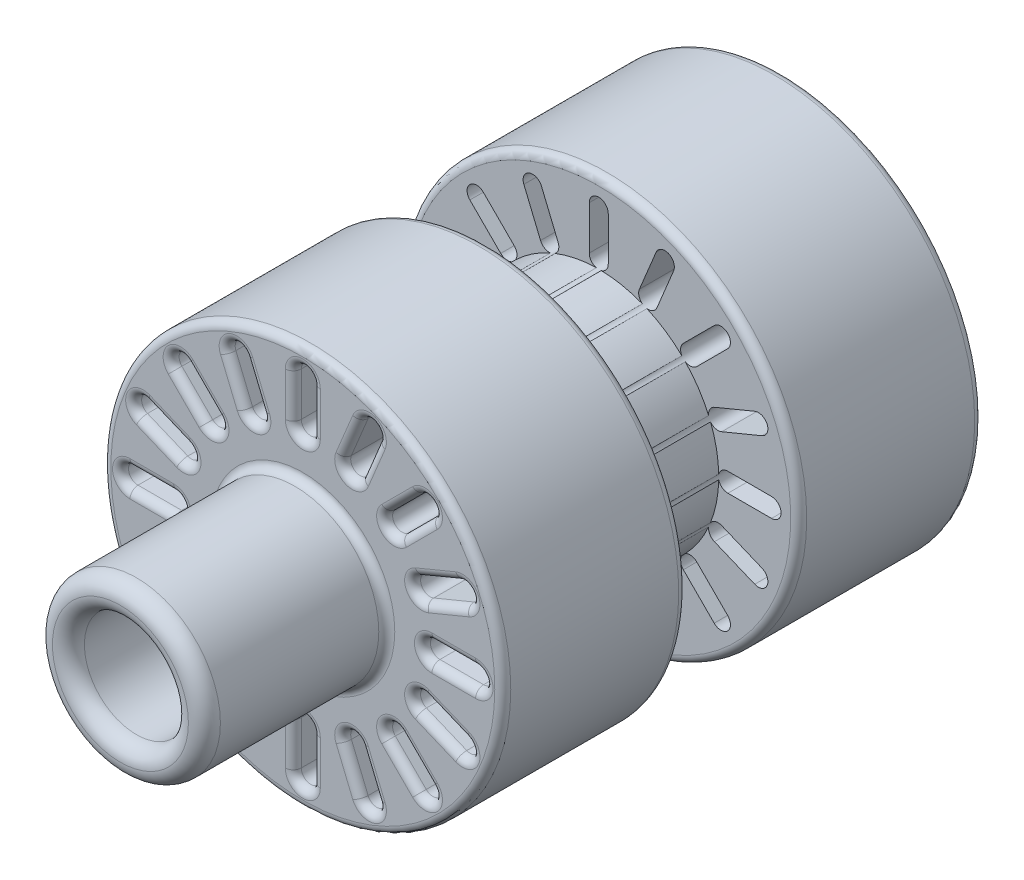
SolidWorks part; units mm, degrees
ref_plane "Front Plane" through (0, 0, 0) normal (0, 0, 1) x (1, 0, 0)
ref_plane "Top Plane" through (0, 0, 0) normal (0, 1, 0) x (1, 0, 0)
ref_plane "Right Plane" through (0, 0, 0) normal (1, 0, 0) x (0, 0, -1)
sketch "Sketch1" plane through (0, 0, 0) normal (1, 0, 0) x (0, 0, -1)
  line L0 (-15, 0) -> (15, 0)
  line L1 (-15, 5.25) -> (-15, 12.5)
  line L2 (-15, 0) -> (15, 0)
  line L3 (-15, 2.15) -> (-15, 3.25)
  line L4 (-15, 12.5) -> (-3.5, 12.5)
  line L5 (15, 6) -> (15, 12.5)
  line L6 (15, 0) -> (3.6, 0)
  line L8 (15, 6) -> (3.6, 6)
  line L9 (3.6, 3.25) -> (3.6, 6)
  line L10 (3.5, 12.5) -> (15, 12.5)
  line L12 (3.5, 12.5) -> (3.5, 7.5)
  line L13 (3.5, 7.5) -> (-3.5, 7.5)
  line L14 (-3.5, 12.5) -> (-3.5, 7.5)
  line L19 (3.6, 0) -> (-15, 0)
  line L21 (3.6, 3.25) -> (-15, 3.25)
  line L22 (-15, 2.15) -> (-15, 3.25)
  line L23 (-15, 3.25) -> (-26.4, 3.25)
  line L25 (-15, 5.25) -> (-26.4, 5.25)
  line L26 (-26.4, 3.25) -> (-26.4, 5.25)
  point P4 (0, 0)
  point P13 (0, 12.5)
  dimension "D1" = 30
  dimension "D2" = 12.5
  dimension "D3" = 11.4
  dimension "D4" = 6
  dimension "D5" = 5
  dimension "D6" = 3.25
  dimension "D7" = 11.4
  dimension "D8" = 2
  dimension "D9" = 1.5
revolve "Revolve1" add sketch "Sketch1" angle 360 about L0 region at (0, 8.875, 14.5758)
sketch "Sketch2" plane through (0, 0, -15) normal (0, 0, -1) x (-1, 0, 0)
  line L0 (0, 6) -> (0, 12.5) construction
  line L1 (0, 12.5) -> (0, 11.3) construction
  line L2 (0, 6) -> (0, 6.0726) construction
  line L3 (0, 11.3) -> (0, 10.8) construction
  line L4 (0, 6.0726) -> (0, 8.0726) construction
  line L5 (0, 10.8) -> (0, 8.0726) construction
  line L6 (0.5941, 10.8) -> (0.5941, 8.0726)
  line L7 (-0.5941, 10.8) -> (-0.5941, 8.0726)
  line L8 (3.5841, 10.2053) -> (2.5403, 7.6854)
  line L9 (4.6819, 9.7505) -> (3.6382, 7.2307)
  line L10 (4.133, 9.9779) -> (3.0892, 7.4581) construction
  line L11 (7.2166, 8.0569) -> (5.288, 6.1283)
  line L12 (8.0569, 7.2166) -> (6.1283, 5.288)
  line L13 (7.6368, 7.6368) -> (5.7082, 5.7082) construction
  line L14 (9.7505, 4.6819) -> (7.2307, 3.6382)
  line L15 (10.2053, 3.5841) -> (7.6854, 2.5403)
  line L16 (9.9779, 4.133) -> (7.4581, 3.0892) construction
  line L17 (10.8, 0.5941) -> (8.0726, 0.5941)
  line L18 (10.8, -0.5941) -> (8.0726, -0.5941)
  line L19 (10.8, 0) -> (8.0726, 0) construction
  line L20 (10.2053, -3.5841) -> (7.6854, -2.5403)
  line L21 (9.7505, -4.6819) -> (7.2307, -3.6382)
  line L22 (9.9779, -4.133) -> (7.4581, -3.0892) construction
  line L23 (8.0569, -7.2166) -> (6.1283, -5.288)
  line L24 (7.2166, -8.0569) -> (5.288, -6.1283)
  line L25 (7.6368, -7.6368) -> (5.7082, -5.7082) construction
  line L26 (4.6819, -9.7505) -> (3.6382, -7.2307)
  line L27 (3.5841, -10.2053) -> (2.5403, -7.6854)
  line L28 (4.133, -9.9779) -> (3.0892, -7.4581) construction
  line L29 (0.5941, -10.8) -> (0.5941, -8.0726)
  line L30 (-0.5941, -10.8) -> (-0.5941, -8.0726)
  line L31 (0, -10.8) -> (0, -8.0726) construction
  line L32 (-3.5841, -10.2053) -> (-2.5403, -7.6854)
  line L33 (-4.6819, -9.7505) -> (-3.6382, -7.2307)
  line L34 (-4.133, -9.9779) -> (-3.0892, -7.4581) construction
  line L35 (-7.2166, -8.0569) -> (-5.288, -6.1283)
  line L36 (-8.0569, -7.2166) -> (-6.1283, -5.288)
  line L37 (-7.6368, -7.6368) -> (-5.7082, -5.7082) construction
  line L38 (-9.7505, -4.6819) -> (-7.2307, -3.6382)
  line L39 (-10.2053, -3.5841) -> (-7.6854, -2.5403)
  line L40 (-9.9779, -4.133) -> (-7.4581, -3.0892) construction
  line L41 (-10.8, -0.5941) -> (-8.0726, -0.5941)
  line L42 (-10.8, 0.5941) -> (-8.0726, 0.5941)
  line L43 (-10.8, 0) -> (-8.0726, 0) construction
  line L44 (-10.2053, 3.5841) -> (-7.6854, 2.5403)
  line L45 (-9.7505, 4.6819) -> (-7.2307, 3.6382)
  line L46 (-9.9779, 4.133) -> (-7.4581, 3.0892) construction
  line L47 (-8.0569, 7.2166) -> (-6.1283, 5.288)
  line L48 (-7.2166, 8.0569) -> (-5.288, 6.1283)
  line L49 (-7.6368, 7.6368) -> (-5.7082, 5.7082) construction
  line L50 (-4.6819, 9.7505) -> (-3.6382, 7.2307)
  line L51 (-3.5841, 10.2053) -> (-2.5403, 7.6854)
  line L52 (-4.133, 9.9779) -> (-3.0892, 7.4581) construction
  circle A0 centre (0, 0) radius 6 construction
  circle A1 centre (0, 0) radius 12.5 construction
  arc A2 (0.5941, 10.8) -> (-0.5941, 10.8) centre (0, 10.8) ccw
  arc A3 (-0.5941, 8.0726) -> (0.5941, 8.0726) centre (0, 8.0726) ccw
  arc A4 (4.6819, 9.7505) -> (3.5841, 10.2053) centre (4.133, 9.9779) ccw
  arc A5 (2.5403, 7.6854) -> (3.6382, 7.2307) centre (3.0892, 7.4581) ccw
  arc A6 (8.0569, 7.2166) -> (7.2166, 8.0569) centre (7.6368, 7.6368) ccw
  arc A7 (5.288, 6.1283) -> (6.1283, 5.288) centre (5.7082, 5.7082) ccw
  arc A8 (10.2053, 3.5841) -> (9.7505, 4.6819) centre (9.9779, 4.133) ccw
  arc A9 (7.2307, 3.6382) -> (7.6854, 2.5403) centre (7.4581, 3.0892) ccw
  arc A10 (10.8, -0.5941) -> (10.8, 0.5941) centre (10.8, 0) ccw
  arc A11 (8.0726, 0.5941) -> (8.0726, -0.5941) centre (8.0726, 0) ccw
  arc A12 (9.7505, -4.6819) -> (10.2053, -3.5841) centre (9.9779, -4.133) ccw
  arc A13 (7.6854, -2.5403) -> (7.2307, -3.6382) centre (7.4581, -3.0892) ccw
  arc A14 (7.2166, -8.0569) -> (8.0569, -7.2166) centre (7.6368, -7.6368) ccw
  arc A15 (6.1283, -5.288) -> (5.288, -6.1283) centre (5.7082, -5.7082) ccw
  arc A16 (3.5841, -10.2053) -> (4.6819, -9.7505) centre (4.133, -9.9779) ccw
  arc A17 (3.6382, -7.2307) -> (2.5403, -7.6854) centre (3.0892, -7.4581) ccw
  arc A18 (-0.5941, -10.8) -> (0.5941, -10.8) centre (0, -10.8) ccw
  arc A19 (0.5941, -8.0726) -> (-0.5941, -8.0726) centre (0, -8.0726) ccw
  arc A20 (-4.6819, -9.7505) -> (-3.5841, -10.2053) centre (-4.133, -9.9779) ccw
  arc A21 (-2.5403, -7.6854) -> (-3.6382, -7.2307) centre (-3.0892, -7.4581) ccw
  arc A22 (-8.0569, -7.2166) -> (-7.2166, -8.0569) centre (-7.6368, -7.6368) ccw
  arc A23 (-5.288, -6.1283) -> (-6.1283, -5.288) centre (-5.7082, -5.7082) ccw
  arc A24 (-10.2053, -3.5841) -> (-9.7505, -4.6819) centre (-9.9779, -4.133) ccw
  arc A25 (-7.2307, -3.6382) -> (-7.6854, -2.5403) centre (-7.4581, -3.0892) ccw
  arc A26 (-10.8, 0.5941) -> (-10.8, -0.5941) centre (-10.8, 0) ccw
  arc A27 (-8.0726, -0.5941) -> (-8.0726, 0.5941) centre (-8.0726, 0) ccw
  arc A28 (-9.7505, 4.6819) -> (-10.2053, 3.5841) centre (-9.9779, 4.133) ccw
  arc A29 (-7.6854, 2.5403) -> (-7.2307, 3.6382) centre (-7.4581, 3.0892) ccw
  arc A30 (-7.2166, 8.0569) -> (-8.0569, 7.2166) centre (-7.6368, 7.6368) ccw
  arc A31 (-6.1283, 5.288) -> (-5.288, 6.1283) centre (-5.7082, 5.7082) ccw
  arc A32 (-3.5841, 10.2053) -> (-4.6819, 9.7505) centre (-4.133, 9.9779) ccw
  arc A33 (-3.6382, 7.2307) -> (-2.5403, 7.6854) centre (-3.0892, 7.4581) ccw
  point P11 (0, 9.4363)
  point P21 (3.6111, 8.718)
  point P28 (6.6725, 6.6725)
  point P35 (8.718, 3.6111)
  point P42 (9.4363, 0)
  point P49 (8.718, -3.6111)
  point P56 (6.6725, -6.6725)
  point P63 (3.6111, -8.718)
  point P70 (0, -9.4363)
  point P77 (-3.6111, -8.718)
  point P84 (-6.6725, -6.6725)
  point P91 (-8.718, -3.6111)
  point P98 (-9.4363, 0)
  point P105 (-8.718, 3.6111)
  point P112 (-6.6725, 6.6725)
  point P119 (-3.6111, 8.718)
  dimension "D1" = 1.2
  dimension "D2" = 0.5
  dimension "D3" = 2
  dimension "D4" = 16
extrude "Cut-Extrude1" cut sketch "Sketch2" against normal blind 86
fillet "Fillet3" radius 0.5 66 edges at (6, 0, -15) (12.5, 0, -15) (0, 7.4784, -15) (-0.5941, 9.4363, -15) (0, 11.3941, -15) (0.5941, 9.4363, -15) (-7.4784, 0, -15) (-9.4363, -0.5941, -15) (-11.3941, 0, -15) (-9.4363, 0.5941, -15) (-6.9092, 2.8619, -15) (-8.9454, 3.0622, -15) (-10.5268, 4.3603, -15) (-8.4906, 4.16, -15) (-2.8619, 6.9092, -15) (-4.16, 8.4906, -15) (-4.3603, 10.5268, -15) (-3.0622, 8.9454, -15) (-5.288, 5.288, -15) (-7.0926, 6.2523, -15) (-8.0569, 8.0569, -15) (-6.2523, 7.0926, -15) (0, -7.4784, -15) (0.5941, -9.4363, -15) (0, -11.3941, -15) (-0.5941, -9.4363, -15) (-2.8619, -6.9092, -15) (-3.0622, -8.9454, -15) (-4.3603, -10.5268, -15) (-4.16, -8.4906, -15) (-6.9092, -2.8619, -15) (-8.4906, -4.16, -15) (-10.5268, -4.3603, -15) (-8.9454, -3.0622, -15) (-5.288, -5.288, -15) (-6.2523, -7.0926, -15) (-8.0569, -8.0569, -15) (-7.0926, -6.2523, -15) (7.4784, 0, -15) (9.4363, 0.5941, -15) (11.3941, 0, -15) (9.4363, -0.5941, -15) (6.9092, -2.8619, -15) (8.9454, -3.0622, -15) (10.5268, -4.3603, -15) (8.4906, -4.16, -15) (2.8619, -6.9092, -15) (4.16, -8.4906, -15) (4.3603, -10.5268, -15) (3.0622, -8.9454, -15) (5.288, -5.288, -15) (7.0926, -6.2523, -15) (8.0569, -8.0569, -15) (6.2523, -7.0926, -15) (2.8619, 6.9092, -15) (3.0622, 8.9454, -15) (4.3603, 10.5268, -15) (4.16, 8.4906, -15) (6.9092, 2.8619, -15) (8.4906, 4.16, -15) (10.5268, 4.3603, -15) (8.9454, 3.0622, -15) (5.288, 5.288, -15) (6.2523, 7.0926, -15) (8.0569, 8.0569, -15) (7.0926, 6.2523, -15)
fillet "Fillet5" radius 0.5 68 edges at (5.25, 0, 15) (12.5, 0, 15) (-0.5941, 9.4363, 15) (0, 7.4784, 15) (0.5941, 9.4363, 15) (0, 11.3941, 15) (-9.4363, -0.5941, 15) (-7.4784, 0, 15) (-9.4363, 0.5941, 15) (-11.3941, 0, 15) (-8.9454, 3.0622, 15) (-6.9092, 2.8619, 15) (-8.4906, 4.16, 15) (-10.5268, 4.3603, 15) (-4.16, 8.4906, 15) (-2.8619, 6.9092, 15) (-3.0622, 8.9454, 15) (-4.3603, 10.5268, 15) (-7.0926, 6.2523, 15) (-5.288, 5.288, 15) (-6.2523, 7.0926, 15) (-8.0569, 8.0569, 15) (0.5941, -9.4363, 15) (0, -7.4784, 15) (-0.5941, -9.4363, 15) (0, -11.3941, 15) (-3.0622, -8.9454, 15) (-2.8619, -6.9092, 15) (-4.16, -8.4906, 15) (-4.3603, -10.5268, 15) (-8.4906, -4.16, 15) (-6.9092, -2.8619, 15) (-8.9454, -3.0622, 15) (-10.5268, -4.3603, 15) (-6.2523, -7.0926, 15) (-5.288, -5.288, 15) (-7.0926, -6.2523, 15) (-8.0569, -8.0569, 15) (9.4363, 0.5941, 15) (7.4784, 0, 15) (9.4363, -0.5941, 15) (11.3941, 0, 15) (8.9454, -3.0622, 15) (6.9092, -2.8619, 15) (8.4906, -4.16, 15) (10.5268, -4.3603, 15) (4.16, -8.4906, 15) (2.8619, -6.9092, 15) (3.0622, -8.9454, 15) (4.3603, -10.5268, 15) (7.0926, -6.2523, 15) (5.288, -5.288, 15) (6.2523, -7.0926, 15) (8.0569, -8.0569, 15) (3.0622, 8.9454, 15) (2.8619, 6.9092, 15) (4.16, 8.4906, 15) (4.3603, 10.5268, 15) (8.4906, 4.16, 15) (6.9092, 2.8619, 15) (8.9454, 3.0622, 15) (10.5268, 4.3603, 15) (6.2523, 7.0926, 15) (5.288, 5.288, 15) (7.0926, 6.2523, 15) (8.0569, 8.0569, 15) (12.5, 0, -3.5) (12.5, 0, 3.5)
fillet "Fillet6" radius 1 2 edges at (3.25, 0, 26.4) (5.25, 0, 26.4)
